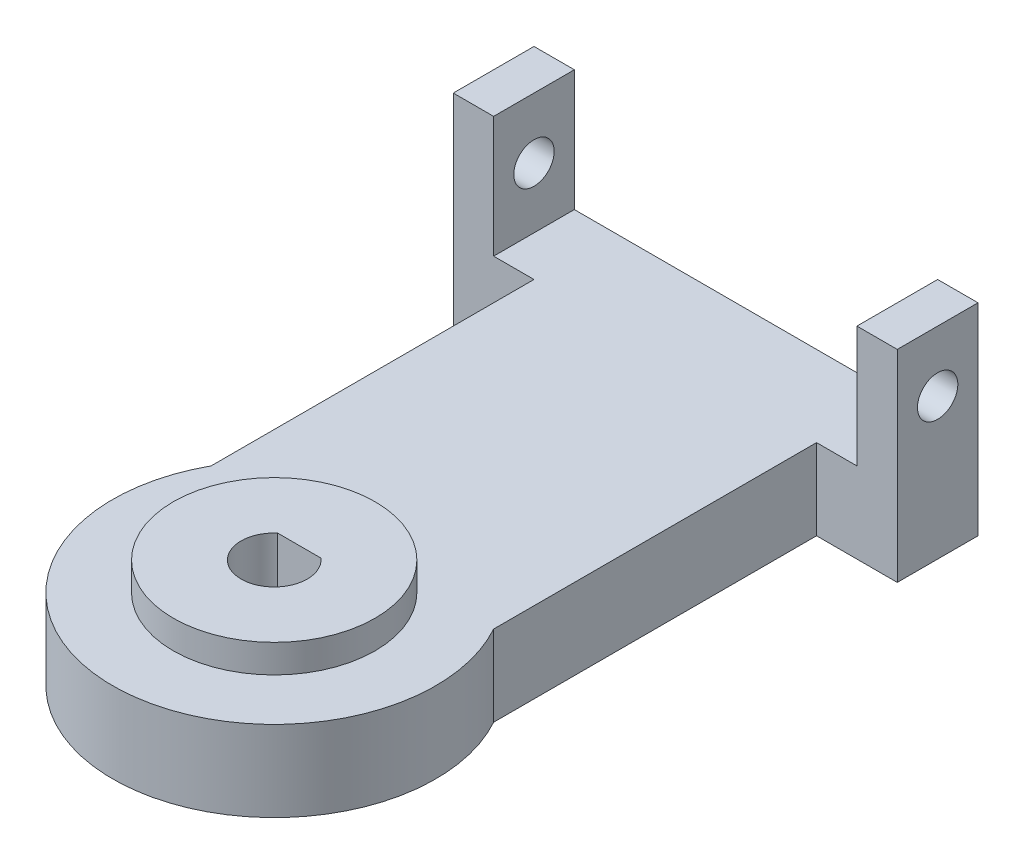
SolidWorks part; units mm, degrees
ref_plane "Front Plane" through (0, 0, 0) normal (0, 0, 1) x (1, 0, 0)
ref_plane "Top Plane" through (0, 0, 0) normal (0, 1, 0) x (1, 0, 0)
ref_plane "Right Plane" through (0, 0, 0) normal (1, 0, 0) x (0, 0, -1)
sketch "Sketch1" plane through (0, 0, 0) normal (0, 1, 0) x (1, 0, 0)
  circle A21 centre (0, 0) radius 20
  dimension "D1" = 40
extrude "Boss-Extrude1" add sketch "Sketch1" along normal blind 10
sketch "Sketch2" plane through (0, 10, 0) normal (0, 1, 0) x (1, 0, 0)
  line L0 (-2.6458, 3) -> (2.6458, 3) construction
  line L1 (-2.6833, 3.1) -> (2.6833, 3.1)
  arc A0 (-2.6458, 3) -> (2.6458, 3) centre (0, 0) ccw construction
  arc A1 (-2.6833, 3.1) -> (2.6833, 3.1) centre (0, 0) ccw
  point P3 (0, 3)
  point P4 (0, 0)
  dimension "D1" = 4
  dimension "D2" = 5.2915
  dimension "D3" = 0.1
extrude "Cut-Extrude1" cut sketch "Sketch2" against normal offset from surface (2.5 mm away) 7.5 up to face at (0, 0, 20)
sketch "Sketch3" plane through (0, 0, 0) normal (0, 1, 0) x (1, 0, 0)
  line L0 (-17.5, 59.6825) -> (-17.5, 9.6825)
  line L1 (-17.5, 59.6825) -> (17.5, 59.6825)
  line L2 (17.5, 59.6825) -> (17.5, 9.6825)
  circle A0 centre (0, 0) radius 20 construction
  arc A1 (17.5, 9.6825) -> (-17.5, 9.6825) centre (0, 0) ccw
  point P6 (0, 59.6825)
  point P9 (0, 20)
  dimension "D1" = 35
  dimension "D2" = 50
extrude "Boss-Extrude2" add sketch "Sketch3" along normal up to surface (10 mm away) up to face at (0, 10, 0.5)
sketch "Sketch6" plane through (0, 10, 0) normal (0, 1, 0) x (1, 0, 0)
  line L5 (-2.6833, 3.1) -> (2.6833, 3.1) construction
  line L6 (-2.6833, 3.1) -> (2.6833, 3.1)
  circle A0 centre (0, 0) radius 12.5
  arc A3 (-2.6833, 3.1) -> (2.6833, 3.1) centre (0, 0) ccw construction
  arc A4 (-2.6833, 3.1) -> (2.6833, 3.1) centre (0, 0) ccw
  dimension "D1" = 25
extrude "Boss-Extrude3" add sketch "Sketch6" along normal blind 6
sketch "Sketch7" plane through (0, 0, -59.6825) normal (0, 0, -1) x (-1, 0, 0)
  line L0 (-27.5, 0) -> (-27.5, 25)
  line L1 (-27.5, 25) -> (-22.5, 25)
  line L2 (-22.5, 25) -> (-22.5, 10)
  line L3 (-17.5, 10) -> (17.5, 10) construction
  line L4 (-22.5, 10) -> (22.5, 10)
  line L5 (22.5, 10) -> (22.5, 25)
  line L6 (22.5, 25) -> (27.5, 25)
  line L7 (27.5, 25) -> (27.5, 0)
  line L8 (27.5, 0) -> (-27.5, 0)
  dimension "D1" = 5
  dimension "D2" = 15
  dimension "D3" = 45
extrude "Boss-Extrude4" add sketch "Sketch7" against normal blind 10
sketch "Sketch8" plane through (-27.5, 0, 0) normal (-1, 0, 0) x (0, 0, 1)
  line L1 (-49.6825, 25) -> (-59.6825, 25) construction
  circle A0 centre (-54.6825, 17.5) radius 2.5
  point P7 (-54.6825, 25)
  dimension "D2" = 5
  dimension "D1" = 7.5
extrude "Cut-Extrude2" cut sketch "Sketch8" against normal through all
sketch "Sketch9" plane through (0, 16, 0) normal (0, 1, 0) x (1, 0, 0)
  circle A0 centre (0, 0) radius 12.5
  circle A1 centre (0, 0) radius 12.5 construction
extrude "Cut-Extrude3" cut sketch "Sketch9" against normal blind 2.5
